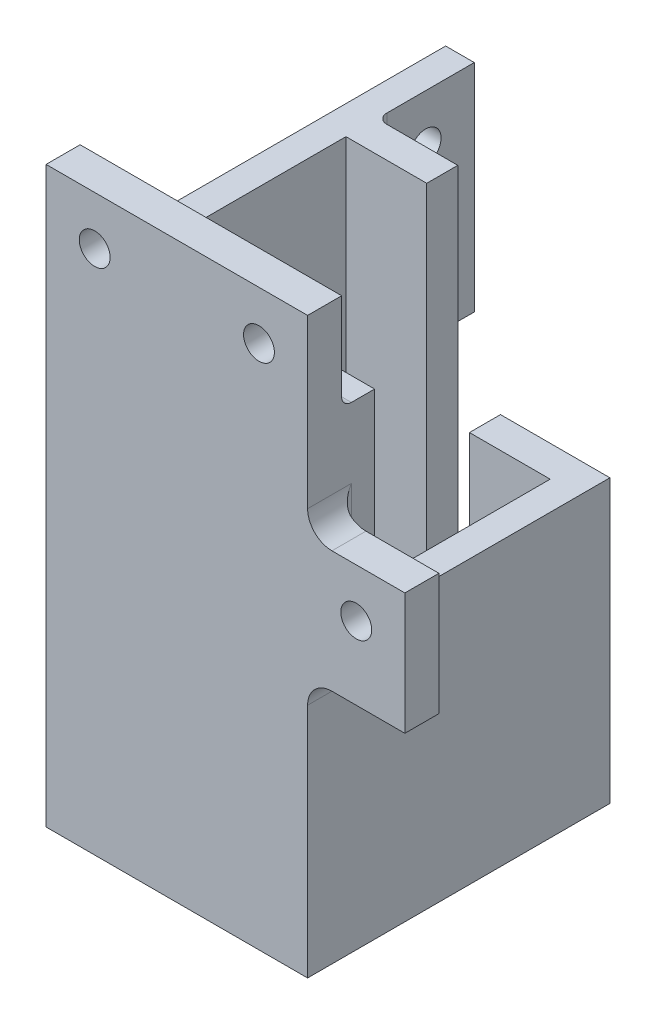
SolidWorks part; units mm, degrees
ref_plane "Front" through (0, 0, 0) normal (0, 0, 1) x (1, 0, 0)
ref_plane "Top" through (0, 0, 0) normal (0, 1, 0) x (1, 0, 0)
ref_plane "Right" through (0, 0, 0) normal (1, 0, 0) x (0, 0, -1)
sketch "Sketch1" plane through (0, 0, 0) normal (0, 1, 0) x (1, 0, 0)
  line L0 (4.39, 21) -> (4.39, 27.39)
  line L1 (-21, 21) -> (-4.39, 21)
  line L2 (-21, 21) -> (-21, -21)
  line L3 (-21, -21) -> (21, -21)
  line L4 (21, 21) -> (21, -21)
  line L5 (-21, 21) -> (21, -21) construction
  line L6 (-21, -21) -> (21, 21) construction
  line L7 (-26.89, 27.39) -> (-4.39, 27.39)
  line L8 (-26.89, 27.39) -> (-26.89, -34.776)
  line L9 (-26.89, -34.776) -> (26.89, -34.776)
  line L10 (26.89, 27.39) -> (26.89, -34.776)
  line L13 (-4.39, 21) -> (-4.39, 27.39)
  line L14 (4.39, 27.39) -> (26.89, 27.39)
  line L15 (4.39, 21) -> (21, 21)
  point P0 (0, 0)
  point P6 (0, 0)
  point P15 (0, -34.776)
  point P16 (26.3954, -25.0081)
  dimension "D1" = 42
  dimension "D2" = 53.78
  dimension "D3" = 22.5
  dimension "D4" = 22.5
  dimension "D6" = 6.39
  dimension "D7" = 62.166
extrude "Boss-Extrude1" add sketch "Sketch1" along normal blind 48
sketch "Sketch2" plane through (0, 0, 0) normal (0, 1, 0) x (1, 0, 0)
  line L0 (-26.89, 27.39) -> (-26.89, -34.776) construction
  line L1 (-26.89, 27.39) -> (26.89, 27.39)
  line L2 (-26.89, 27.39) -> (-26.89, -34.776)
  line L3 (-26.89, -34.776) -> (26.89, -34.776)
  line L4 (26.89, 27.39) -> (26.89, -34.776)
  line L5 (26.89, -34.776) -> (26.89, 27.39) construction
  line L6 (-26.89, -34.776) -> (26.89, -34.776) construction
  line L7 (26.89, 27.39) -> (4.39, 27.39) construction
  point P0 (0, 0)
extrude "Boss-Extrude2" add sketch "Sketch2" against normal blind 10
sketch "Sketch3" plane through (0, 48, 0) normal (0, 1, 0) x (1, 0, 0)
  line L1 (26.89, -21) -> (26.89, -27.776)
  line L3 (26.89, -21) -> (-21, -21)
  line L4 (-26.89, 27.39) -> (-26.89, -34.776) construction
  line L6 (-26.89, -34.776) -> (26.89, -34.776) construction
  line L7 (-26.89, -34.776) -> (46.89, -34.776)
  line L8 (26.89, -34.776) -> (26.89, 27.39) construction
  line L10 (26.89, -27.776) -> (46.89, -27.776)
  line L11 (21, -21) -> (-21, -21) construction
  line L13 (-21, -21) -> (-21, 47.39)
  line L14 (46.89, -27.776) -> (46.89, -34.776)
  line L16 (-26.89, -34.776) -> (-26.89, 47.39)
  line L17 (-21, 47.39) -> (-26.89, 47.39)
  line L18 (-4.39, 27.39) -> (-26.89, 27.39) construction
  dimension "D1" = 20
  dimension "D2" = 20
  dimension "D3" = 7
extrude "Boss-Extrude3" add sketch "Sketch3" along normal blind 40 and the other way up to surface (4.425 mm away)
sketch "Sketch6" plane through (0, 0, 27.776) normal (0, 0, -1) x (-1, 0, 0)
  line L0 (-26.89, 88) -> (-46.89, 88)
  line L1 (-46.89, 88) -> (-46.89, 68.575)
  line L2 (-46.89, 43.575) -> (-46.89, 88) construction
  line L3 (-46.89, 68.575) -> (-26.89, 68.575)
  line L4 (-26.89, 43.575) -> (-26.89, 88) construction
  line L5 (-26.89, 68.575) -> (-26.89, 88)
  line L6 (-26.89, 43.575) -> (-46.89, 43.575) construction
  dimension "D1" = 25
extrude "Cut-Extrude3" cut sketch "Sketch6" against normal through all
sketch "Sketch7" plane through (0, 88, 0) normal (0, 1, 0) x (1, 0, 0)
  line L0 (26.89, -34.776) -> (26.89, -27.776)
  line L1 (26.89, -34.776) -> (26.89, -21) construction
  line L2 (26.89, -27.776) -> (-26.89, -27.776)
  line L3 (-26.89, 47.39) -> (-26.89, -34.776) construction
  line L4 (-26.89, -27.776) -> (-26.89, -34.776)
  line L5 (-26.89, -34.776) -> (26.89, -34.776)
  dimension "D1" = 7
extrude "Boss-Extrude4" add sketch "Sketch7" along normal blind 20
sketch "Sketch9" plane through (0, 48, 0) normal (0, 1, 0) x (1, 0, 0)
  line L0 (-21, 21) -> (-21, 27.39)
  line L1 (-21, 27.39) -> (-4.39, 27.39)
  line L2 (-4.39, 27.39) -> (-4.39, 21)
  line L3 (-4.39, 21) -> (-21, 21)
extrude "Boss-Extrude5" add sketch "Sketch9" along normal up to surface (40 mm away) up to face at (-7, 88, 0.462)
sketch "Sketch4" plane through (-21, 0, 0) normal (1, 0, 0) x (0, 0, -1)
  line L0 (-21, 88) -> (21, 88) construction
  line L1 (47.39, 43.575) -> (27.39, 43.575) construction
  circle A0 centre (37.39, 78) radius 3.175
  circle A1 centre (37.39, 58.575) radius 3.175
  point P9 (37.39, 43.575)
  dimension "D1" = 6.35
  dimension "D3" = 15
  dimension "D2" = 10
extrude "Cut-Extrude1" cut sketch "Sketch4" against normal through all
sketch "Sketch5" plane through (0, 0, 27.776) normal (0, 0, 1) x (1, 0, 0)
  line L2 (46.89, 88) -> (26.89, 88) construction
  line L3 (26.89, 43.575) -> (46.89, 43.575) construction
  circle A1 centre (36.89, 58.575) radius 3.175
  point P0 (0, 0)
  point P9 (36.89, 88)
  dimension "D1" = 6.35
  dimension "D3" = 15
extrude "Cut-Extrude2" cut sketch "Sketch5" along normal through all contours A1
sketch "Sketch8" plane through (0, 0, 27.776) normal (0, 0, -1) x (-1, 0, 0)
  line L0 (-26.89, 108) -> (-26.89, 88) construction
  line L1 (26.89, 108) -> (26.89, 88) construction
  circle A0 centre (-16.89, 98) radius 3.175
  circle A1 centre (16.89, 98) radius 3.175
  point P4 (0, 0)
  point P5 (0, 0)
  point P8 (-26.89, 98)
  dimension "D1" = 6.35
  dimension "D2" = 10
  dimension "D3" = 10
extrude "Cut-Extrude4" cut sketch "Sketch8" against normal through all
fillet "Fillet1" radius 2 3 edges at (26.89, 56.075, 27.776) (0, 88, 27.776) (-21, 65.7875, -27.39)
fillet "Fillet2" radius 5 3 edges at (-22.945, 43.575, -27.39) (26.89, 43.575, 30.276) (26.89, 68.575, 30.276)
